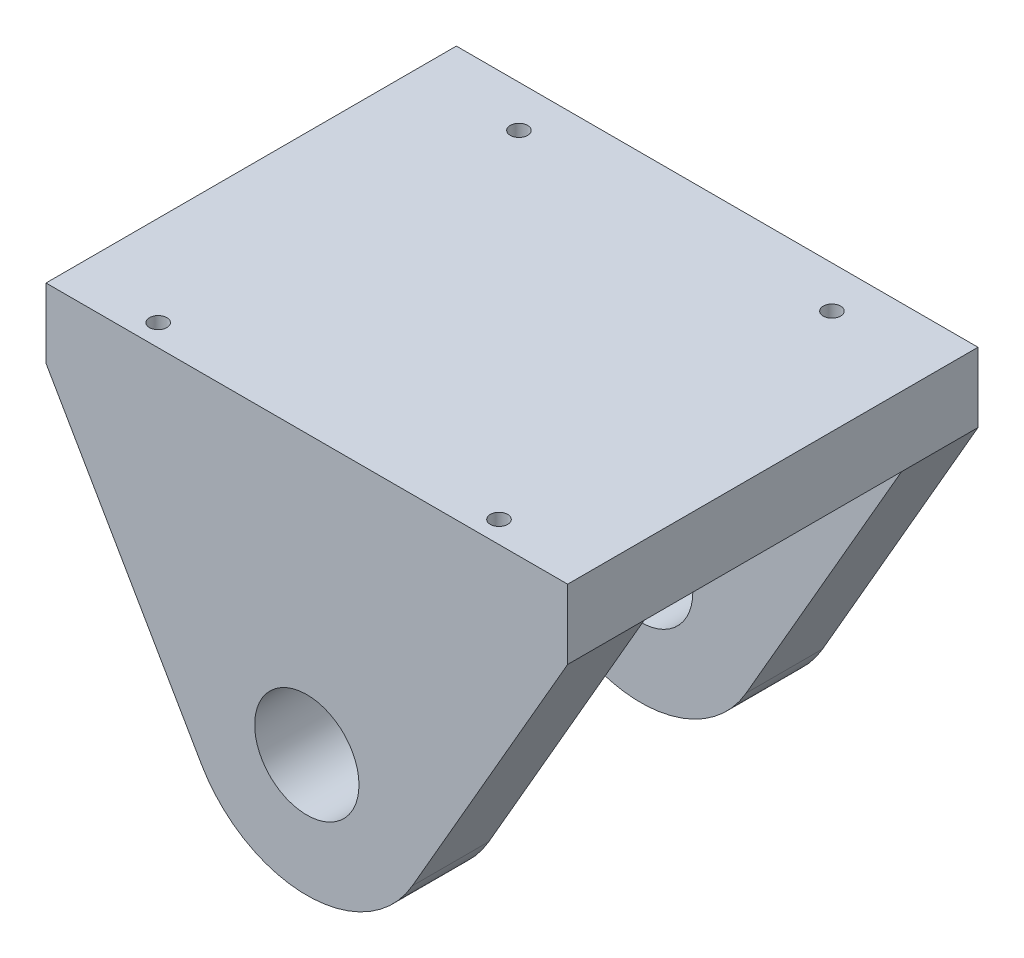
SolidWorks part; units mm, degrees
ref_plane "Front Plane" through (0, 0, 0) normal (0, 0, 1) x (1, 0, 0)
ref_plane "Top Plane" through (0, 0, 0) normal (0, 1, 0) x (1, 0, 0)
ref_plane "Right Plane" through (0, 0, 0) normal (1, 0, 0) x (0, 0, -1)
sketch "Sketch1" plane through (0, 0, 0) normal (0, 0, 1) x (1, 0, 0)
  line L0 (-3, 6.8739) -> (3, 6.8739)
  line L1 (-37.5, 30) -> (37.5, 30)
  line L2 (-15.1601, -8.7419) -> (-37.5, 30)
  line L3 (15.1601, -8.7419) -> (37.5, 30)
  line L4 (-37.5, 30) -> (-37.5, 40)
  line L5 (-37.5, 40) -> (37.5, 40)
  line L6 (37.5, 40) -> (37.5, 30)
  circle A0 centre (0, 0) radius 17.5
  circle A1 centre (0, 0) radius 7.5
  dimension "D1" = 35
  dimension "D2" = 15
  dimension "D3" = 6
  dimension "D4" = 30
  dimension "D5" = 75
  dimension "D7" = 10
extrude "Boss-Extrude1" add sketch "Sketch1" against normal blind 11 contours A0 L3 L1 L2 | A0 A1 region at (0, 19.7022, 0) region at (-4.3968, 16.4268, 0)
extrude "Boss-Extrude2" add sketch "Sketch1<3>" against normal blind 59 contours L6 L5 L4 L1 region at (0, 35, 0)
sketch "Sketch1<3>" plane through (0, 0, 0) normal (0, 0, 1) x (1, 0, 0) same geometry as "Sketch1"
ref_plane "Plane2" through (0, 0, -29.5) normal (0, 0, 1) x (1, 0, 0)
mirror "Mirror2" about plane through (0, 0, -29.5) normal (0, 0, 1) of "Boss-Extrude1"
hole_wizard "Tap Drill for M3x0.5 Tap1" positions "Sketch2" profile "Sketch3" hole size "M3x0.5" standard "ANSI Metric"
sketch "Sketch2" plane through (0, 40, 0) normal (0, 1, 0) x (1, 0, 0)
  line L0 (-37.5, 53) -> (37.5, 53) construction
  line L1 (-37.5, 59) -> (-37.5, 0) construction
  line L2 (37.5, 59) -> (37.5, 0) construction
  line L4 (-24.5, 59) -> (-24.5, 0) construction
  line L5 (-37.5, 59) -> (37.5, 59) construction
  line L6 (-37.5, 0) -> (37.5, 0) construction
  line L9 (24.5, 59) -> (24.5, 0) construction
  line L11 (-37.5, 3.13) -> (37.5, 3.13) construction
  line L17 (-22.5, 59) -> (-22.5, 53) construction
  line L20 (22.5, 59) -> (22.5, 53) construction
  point P0 (-22.5, 53)
  point P2 (22.5, 53)
  point P4 (-24.5, 3.13)
  point P6 (24.5, 3.13)
  dimension "D1" = 6
  dimension "D2" = 13
  dimension "D3" = 13
  dimension "D4" = 3.13
  dimension "D5" = 15
  dimension "D6" = 15
sketch "Sketch3" plane through (-22.5, 40, -53) normal (1, 0, 0) x (0, 0, 1)
  line L0 (0, 0) -> (0, 8.7511)
  line L1 (0, 8.7511) -> (1.25, 8)
  line L2 (1.25, 8) -> (1.25, 0)
  line L5 (1.25, 0) -> (0, 0)
  line L10 (0, 8.7511) -> (-1.25, 8) construction
  line L11 (0, -6.35) -> (0, 107.95) construction
  dimension "Hole Dia." = 2.5
  dimension "Hole Depth" = 8
  dimension "Drill Angle" = 118
